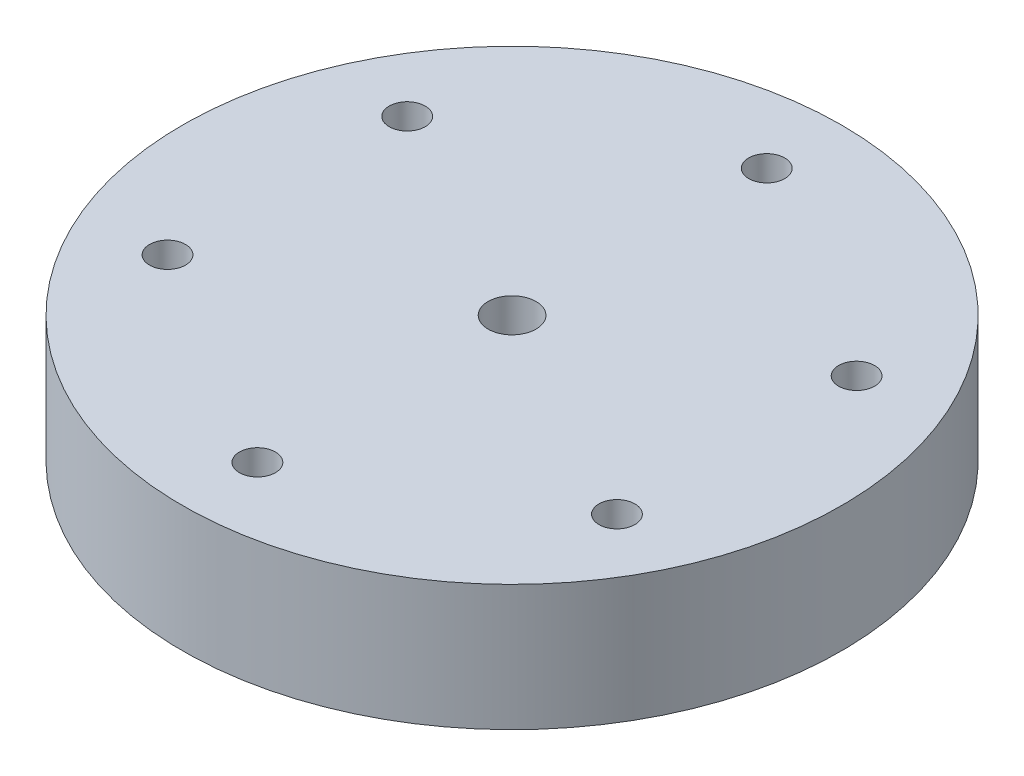
SolidWorks part; units mm, degrees
ref_plane "Front Plane" through (0, 0, 0) normal (0, 0, 1) x (1, 0, 0)
ref_plane "Top Plane" through (0, 0, 0) normal (0, 1, 0) x (1, 0, 0)
ref_plane "Right Plane" through (0, 0, 0) normal (1, 0, 0) x (0, 0, -1)
sketch "Sketch1" plane through (0, 0, 0) normal (0, 1, 0) x (1, 0, 0)
  circle A0 centre (0, 0) radius 55
  circle A1 centre (0, 0) radius 4
  dimension "D1" = 110
  dimension "D2" = 8
extrude "Boss-Extrude1" add sketch "Sketch1" along normal blind 21
sketch "Sketch2" plane through (0, 0, 0) normal (0, 1, 0) x (1, 0, 0)
  line L0 (-37.5, 0) -> (37.5, 0) construction
  line L1 (0, 0) -> (0, 55) construction
  line L2 (-37.5, -20) -> (-37.5, 20) construction
  line L3 (37.5, -20) -> (37.5, 20) construction
  line L4 (0, 0) -> (0, 42.5) construction
  circle A0 centre (0, 0) radius 55 construction
  circle A1 centre (-37.5, 20) radius 3
  circle A2 centre (-37.5, -20) radius 3
  circle A3 centre (37.5, -20) radius 3
  circle A4 centre (37.5, 20) radius 3
  circle A5 centre (0, 42.5) radius 3
  circle A6 centre (0, -42.5) radius 3
  point P15 (0, -42.5)
  point P20 (0, 0)
  point P21 (0, 0)
  dimension "D2" = 6
  dimension "D5" = 6
  dimension "D6" = 6
  dimension "D1" = 75
  dimension "D3" = 40
  dimension "D4" = 42.5
extrude "Cut-Extrude3" cut sketch "Sketch2" against normal blind 10 and the other way through all contours A4 | A3 | A2 | A1 | A5 | A6 region at (-37.5, 0, -20) region at (-37.5, 0, 20) region at (37.5, 0, 20) region at (37.5, 0, -20) region at (0, 0, -42.5) region at (0, 0, 42.5)
sketch "Sketch3" plane through (0, 0, 0) normal (0, 1, 0) x (1, 0, 0)
  line L0 (37.5, -20) -> (37.5, 20) construction
  line L1 (-37.5, -20) -> (-37.5, 20) construction
  line L2 (-37.5, 0) -> (37.5, 0) construction
  line L3 (37.5, -20) -> (37.5, 20) construction
  line L4 (-37.5, -20) -> (-37.5, 20) construction
  line L5 (-37.5, 0) -> (37.5, 0) construction
  line L6 (0, 0) -> (0, 55) construction
  line L7 (0, 0) -> (0, 55) construction
  circle A0 centre (-37.5, 20) radius 5
  circle A1 centre (-37.5, -20) radius 5
  circle A2 centre (37.5, 20) radius 5
  circle A3 centre (37.5, -20) radius 5
  circle A4 centre (0, 42.5) radius 5
  circle A5 centre (0, -42.5) radius 5
  point P12 (0, 42.5)
  point P14 (0, -42.5)
  dimension "D1" = 10
  dimension "D2" = 10
  dimension "D3" = 10
extrude "Cut-Extrude4" cut sketch "Sketch3" along normal blind 5
